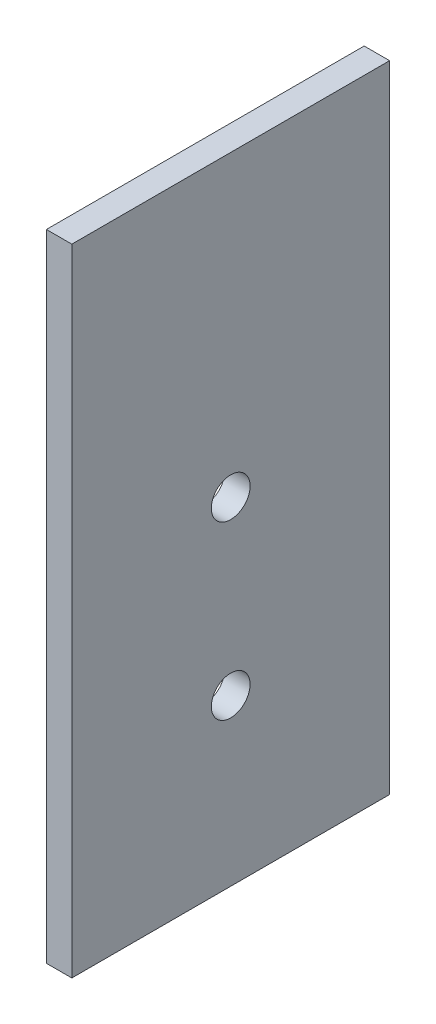
SolidWorks part; units mm, degrees
ref_plane "Front Plane" through (0, 0, 0) normal (0, 0, 1) x (1, 0, 0)
ref_plane "Top Plane" through (0, 0, 0) normal (0, 1, 0) x (1, 0, 0)
ref_plane "Right Plane" through (0, 0, 0) normal (1, 0, 0) x (0, 0, -1)
sketch "Sketch1" plane through (0, 0, 0) normal (1, 0, 0) x (0, 0, -1)
  line L1 (-25, 33.1044) -> (0, 33.1044)
  line L2 (-25, 33.1044) -> (-25, -16.8956)
  line L3 (-25, -16.8956) -> (0, -16.8956)
  line L4 (0, 33.1044) -> (0, -16.8956)
  dimension "D1" = 50
  dimension "D2" = 25
extrude "Boss-Extrude1" add sketch "Sketch1" along normal blind 2
sketch "Sketch3" plane through (0, 0, 0) normal (-1, 0, 0) x (0, 0, 1)
  line L0 (25, -16.8956) -> (0, -16.8956) construction
  line L1 (25, 33.1044) -> (25, -16.8956) construction
  circle A0 centre (12.5, -3.8956) radius 1.525
  circle A1 centre (12.5, 9.6144) radius 1.525
  dimension "D1" = 3.05
  dimension "D2" = 3.05
  dimension "D3" = 13
  dimension "D4" = 13.51
  dimension "D5" = 12.5
extrude "Cut-Extrude1" cut sketch "Sketch3" against normal through all
